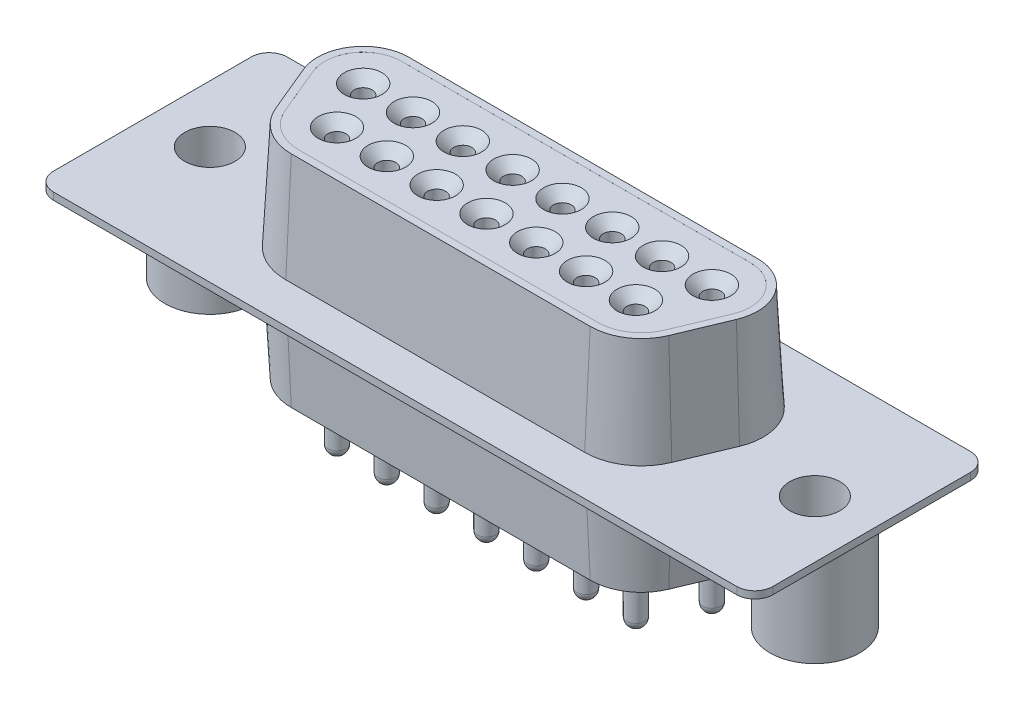
SolidWorks part; units mm, degrees
ref_plane "Front" through (0, 0, 0) normal (0, 0, 1) x (1, 0, 0)
ref_plane "Top" through (0, 0, 0) normal (0, 1, 0) x (1, 0, 0)
ref_plane "Right" through (0, 0, 0) normal (1, 0, 0) x (0, 0, -1)
sketch "Sketch1" plane through (0, 0, 0) normal (0, 1, 0) x (1, 0, 0)
  line L0 (0, 2.54) -> (19.39, 2.54)
  line L1 (1.385, -5.38) -> (18.005, -5.38)
  line L2 (20.626, -3.6337) -> (21.7341, -0.9782)
  line L3 (9.695, 2.54) -> (9.695, -5.38) construction
  line L4 (-1.236, -3.6337) -> (-2.3441, -0.9782)
  arc A0 (18.005, -5.38) -> (20.626, -3.6337) centre (18.005, -2.54) ccw
  arc A1 (21.7341, -0.9782) -> (19.39, 2.54) centre (19.39, 0) ccw
  arc A2 (-2.3441, -0.9782) -> (0, 2.54) centre (0, 0) cw
  arc A3 (1.385, -5.38) -> (-1.236, -3.6337) centre (1.385, -2.54) cw
  dimension "D3" = 2.84
  dimension "D6" = 2.54
  dimension "D1" = 19.39
  dimension "D2" = 16.62
  dimension "D4" = 2.54
  dimension "D5" = 7.92
extrude "Base-Extrude" add sketch "Sketch1" against normal blind 5.91 draft 3 draft outward yes
sketch "Sketch2" plane through (0, -5.91, 0) normal (0, -1, 0) x (1, 0, 0)
  line L0 (9.695, -2.8497) -> (9.695, -5.08) construction
  line L1 (28.695, 7.92) -> (-9.305, 7.92)
  line L2 (29.695, 6.92) -> (29.695, -4.08)
  line L3 (28.695, -5.08) -> (-9.305, -5.08)
  line L4 (-10.305, 6.92) -> (-10.305, -4.08)
  line L5 (19.39, -2.8497) -> (0, -2.8497) construction
  line L6 (9.695, -2.8497) -> (9.695, 5.6897) construction
  line L7 (1.385, 5.6897) -> (18.005, 5.6897) construction
  line L8 (9.695, 1.42) -> (29.695, 1.42) construction
  arc A0 (29.695, 6.92) -> (28.695, 7.92) centre (28.695, 6.92) ccw
  arc A1 (28.695, -5.08) -> (29.695, -4.08) centre (28.695, -4.08) ccw
  arc A2 (-10.305, 6.92) -> (-9.305, 7.92) centre (-9.305, 6.92) cw
  arc A3 (-10.305, -4.08) -> (-9.305, -5.08) centre (-9.305, -4.08) ccw
  point P15 (29.695, 7.92)
  point P18 (29.695, -5.08)
  point P23 (-10.305, -5.08)
  dimension "D3" = 1
  dimension "D1" = 40
  dimension "D2" = 13
extrude "Boss-Extrude1" add sketch "Sketch2" along normal blind 0.2
sketch "Sketch3" plane through (0, 0, 0) normal (0, 1, 0) x (-1, 0, 0)
  line L8 (-19.39, -2.14) -> (0, -2.14)
  line L9 (1.9749, 0.8241) -> (0.8668, 3.4797)
  line L10 (-1.385, 4.98) -> (-18.005, 4.98)
  line L11 (-20.2568, 3.4797) -> (-21.3649, 0.8241)
  line L12 (-19.39, -2.14) -> (0, -2.14)
  line L13 (1.9749, 0.8241) -> (0.8668, 3.4797)
  line L14 (-1.385, 4.98) -> (-18.005, 4.98)
  line L15 (-20.2568, 3.4797) -> (-21.3649, 0.8241)
  arc A8 (0, -2.14) -> (1.9749, 0.8241) centre (0, 0) ccw
  arc A9 (0.8668, 3.4797) -> (-1.385, 4.98) centre (-1.385, 2.54) ccw
  arc A10 (-18.005, 4.98) -> (-20.2568, 3.4797) centre (-18.005, 2.54) ccw
  arc A11 (-21.3649, 0.8241) -> (-19.39, -2.14) centre (-19.39, 0) ccw
  arc A12 (0, -2.14) -> (1.9749, 0.8241) centre (0, 0) ccw
  arc A13 (0.8668, 3.4797) -> (-1.385, 4.98) centre (-1.385, 2.54) ccw
  arc A14 (-18.005, 4.98) -> (-20.2568, 3.4797) centre (-18.005, 2.54) ccw
  arc A15 (-21.3649, 0.8241) -> (-19.39, -2.14) centre (-19.39, 0) ccw
  dimension "D1" = 0.4
extrude "Cut-Extrude1" cut sketch "Sketch3" against normal blind 0.001
mirror "Boss-Mirror1" about plane through (28.695, -6.11, 6.92) normal (0, -1, 0) of bodies 103
sketch "Sketch4" plane through (0, -0.001, 0) normal (0, 1, 0) x (-1, 0, 0)
  circle A0 centre (0, 0) radius 0.5
  dimension "D1" = 1
extrude "Cut-Extrude5" cut sketch "Sketch4" against normal blind 6
sketch "Sketch5" plane through (0, -12.219, 0) normal (0, -1, 0) x (1, 0, 0)
  circle A1 centre (0, 0) radius 0.5
  circle A2 centre (0, 0) radius 0.5 construction
extrude "Boss-Extrude5" add sketch "Sketch5" along normal blind 3
dome "Dome3" faces to dome 1 distance 0.5 reverse direction no elliptical dome no face at (0, -15.219, -0.5) parameters "D1"=0.5
chamfer "Chamfer1" distance 0.55 angle 45 1 edges at (0, -0.001, 0.5)
pattern_linear "LPattern1" count 8 spacing 2.77 along (1, 0, 0) of "Chamfer1", "Dome3", "Boss-Extrude5", "Cut-Extrude5"
sketch "Sketch6" plane through (0, -0.001, 0) normal (0, 1, 0) x (-1, 0, 0)
  line L0 (0, 0) -> (-2.77, 0) construction
  line L1 (-1.385, 0) -> (-1.385, 2.84) construction
  circle A0 centre (-1.385, 2.84) radius 0.5
  circle A3 centre (0, 0) radius 0.5 construction
  circle A4 centre (-2.77, 0) radius 0.5 construction
  dimension "D1" = 2.84
extrude "Cut-Extrude8" cut sketch "Sketch6" against normal blind 6
sketch "Sketch7" plane through (0, -12.219, 0) normal (0, -1, 0) x (1, 0, 0)
  circle A1 centre (1.385, 2.84) radius 0.5
extrude "Boss-Extrude6" add sketch "Sketch7" along normal blind 3
dome "Dome4" faces to dome 1 distance 0.5 reverse direction no elliptical dome no face at (1.385, -15.219, 2.34) parameters "D1"=0.5
chamfer "Chamfer3" distance 0.55 angle 45 1 edges at (1.385, -0.001, 3.34)
pattern_linear "LPattern3" count 7 spacing 2.77 along (1, 0, 0) of "Chamfer3", "Cut-Extrude8", "Boss-Extrude6", "Dome4"
ref_plane "Plane1" through (9.695, 0, 0) normal (1, 0, 0) x (0, 0, -1)
sketch "Sketch8" plane through (0, -6.31, 0) normal (0, 1, 0) x (-1, 0, 0)
  line L0 (-29.695, -4.08) -> (-29.695, 6.92) construction
  line L1 (9.305, -5.08) -> (-28.695, -5.08) construction
  circle A0 centre (-26.515, 1.4) radius 2.5
  dimension "D1" = 5
  dimension "D2" = 3.18
  dimension "D3" = 6.48
extrude "Boss-Extrude4" add sketch "Sketch8" against normal blind 5.9
sketch "Sketch9" plane through (0, -12.21, 0) normal (0, -1, 0) x (1, 0, 0)
  circle A0 centre (26.515, 1.4) radius 1.4
  circle A1 centre (26.515, 1.4) radius 2.5 construction
  dimension "D1" = 2.8
extrude "Cut-Extrude4" cut sketch "Sketch9" against normal through all
mirror "Mirror1" about plane through (9.695, 0, 0) normal (1, 0, 0) of "Boss-Extrude4", "Cut-Extrude4"
